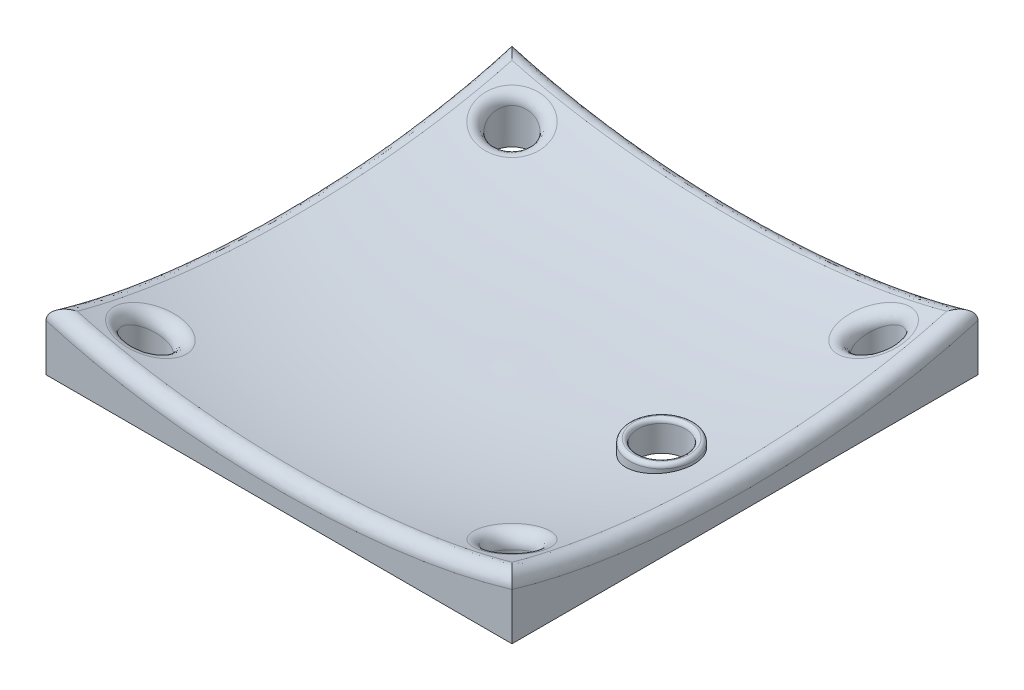
SolidWorks part; units mm, degrees
ref_plane "Front Plane" through (0, 0, 0) normal (0, 0, 1) x (1, 0, 0)
ref_plane "Top Plane" through (0, 0, 0) normal (0, 1, 0) x (1, 0, 0)
ref_plane "Right Plane" through (0, 0, 0) normal (1, 0, 0) x (0, 0, -1)
sketch "Sketch2" plane through (0, 0, 0) normal (0, 0, 1) x (1, 0, 0)
  line L0 (0, 0) -> (0, 146.9297) construction
  line L1 (0, 0) -> (300, 0)
  line L2 (0, 0) -> (0, 4)
  line L4 (300, 0) -> (300, 120)
  spline S0 degree 3 poles (0, 4) (188.6608, 0.9766) (180.522, 94.3059) (300, 120) knots 0 0 0 0 0.603758 0.603758 0.603758 0.603758
  dimension "D1" = 300
  dimension "D2" = 4
  dimension "D3" = 120
revolve "Revolve1" add sketch "Sketch2" angle 360 about L0
sketch "Sketch3" plane through (0, 0, 0) normal (0, -1, 0) x (-1, 0, 0)
  line L0 (-393.6, 393.6) -> (393.6, 393.6)
  line L1 (-93.6, 93.6) -> (93.6, 93.6)
  line L2 (-93.6, 93.6) -> (-93.6, -93.6)
  line L3 (-93.6, -93.6) -> (93.6, -93.6)
  line L4 (93.6, 93.6) -> (93.6, -93.6)
  line L5 (393.6, 393.6) -> (393.6, -393.6)
  line L6 (-393.6, -393.6) -> (393.6, -393.6)
  line L7 (-393.6, 393.6) -> (-393.6, -393.6)
  dimension "D1" = 93.6
  dimension "D2" = 93.6
  dimension "D3" = 93.6
  dimension "D4" = 93.6
  dimension "D5" = 300
extrude "Cut-Extrude1" cut sketch "Sketch3" against normal through all
fillet "Fillet1" radius 5 4 edges at (52.0732, 16.4459, -93.6) (93.6, 16.4459, 52.0732) (-52.0732, 16.4459, 93.6) (-93.6, 16.4459, -52.0732)
sketch "Sketch5" plane through (0, 0, 0) normal (0, -1, 0) x (-1, 0, 0)
  circle A0 centre (-64.1509, -4.05) radius 9.6
  dimension "D1" = 19.2
extrude "Cut-Extrude2" cut sketch "Sketch5" against normal through all
sketch "Sketch6" plane through (0, 0, 0) normal (0, -1, 0) x (-1, 0, 0)
  circle A0 centre (-64.1509, -4.05) radius 9.6
  circle A1 centre (-64.1509, -4.05) radius 12.8
  dimension "D2" = 19.2
  dimension "D1" = 3.2
extrude "Boss-Extrude2" add sketch "Sketch6" against normal blind 12
fillet "Fillet3" radius 1.6 2 edges at (64.1509, 12, -8.75) (64.1509, 12, -5.55)
sketch "Sketch7" plane through (0, 0, 0) normal (0, -1, 0) x (-1, 0, 0)
  line L0 (-93.6, 93.6) -> (-93.6, -93.6) construction
  line L1 (-93.6, -93.6) -> (93.6, -93.6) construction
  circle A0 centre (-73.6, -73.6) radius 8
  circle A1 centre (-73.6, 73.6) radius 8
  circle A2 centre (73.6, 73.6) radius 8
  circle A3 centre (73.6, -73.6) radius 8
  point P15 (0, 0)
  dimension "D3" = 16
  dimension "D1" = 20
  dimension "D2" = 20
  dimension "D4" = 4
extrude "Cut-Extrude3" cut sketch "Sketch7" against normal blind 96
fillet "Fillet4" radius 5 4 edges at (-71.8719, 13.7345, -65.7889) (-71.699, 16.8572, 81.3709) (75.3658, 17.6412, 81.4027) (75.5739, 14.4749, -65.8473)
equation "\"D3@Sketch3\"=\"D1@Sketch3\""
equation "\"D4@Sketch3\"=\"D1@Sketch3\""
equation "\"D2@Sketch3\"=\"D1@Sketch3\""
equation "\"D1@Sketch3\"=100-6.4"
equation "\"D1@Sketch5\"=0.8*24"
equation "\"D2@Sketch6\"=0.8*24"
